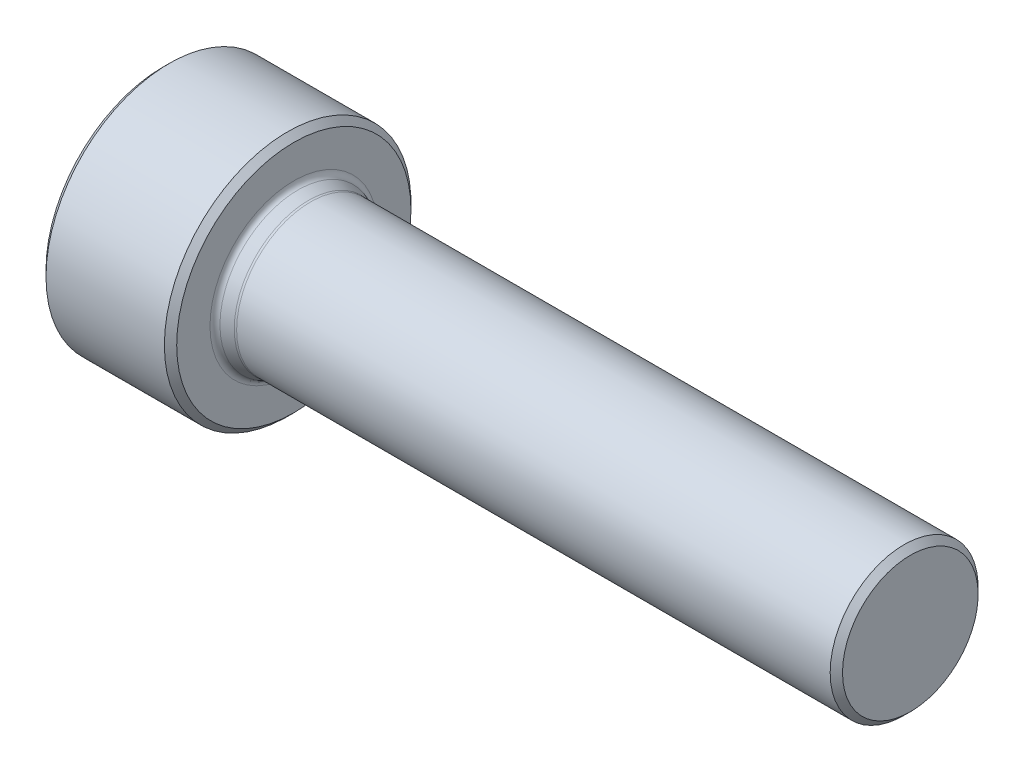
SolidWorks part; units mm, degrees
material "AISI 1020"
ref_plane "Спереди" through (0, 0, 0) normal (0, 0, 1) x (1, 0, 0)
ref_plane "Сверху" through (0, 0, 0) normal (0, 1, 0) x (1, 0, 0)
ref_plane "Справа" through (0, 0, 0) normal (1, 0, 0) x (0, 0, -1)
sketch "Эскиз1" plane through (0, 0, 0) normal (0, 0, 1) x (1, 0, 0)
  line L0 (-1000, 0) -> (49000, 0) construction
  line L1 (-4.9825, 2.5) -> (-5.3, 3.05)
  line L2 (-5.3, 3.05) -> (-5.3, 5)
  line L3 (-5.3, 5) -> (0, 5)
  line L4 (0, 5) -> (0, 3.4)
  line L5 (0.1677, 3.1639) -> (0.5977, 3.0139)
  line L6 (0.68, 3) -> (25, 3)
  line L7 (25, 3) -> (25, 0)
  line L8 (-4.9825, 2.5) -> (-2.3, 2.5)
  line L9 (-2.3, 2.5) -> (-0.8566, 0)
  line L10 (25, 0) -> (-0.8566, 0)
  arc A0 (0.5977, 3.0139) -> (0.68, 3) centre (0.68, 3.25) ccw
  arc A1 (0, 3.4) -> (0.1677, 3.1639) centre (0.25, 3.4) ccw
  dimension "c" = 0.25
  dimension "UGOL" = 60
  dimension "D" = 10
  dimension "t" = 3
  dimension "w" = 2.3
  dimension "l" = 25
  dimension "D_1" = 6.1
  dimension "S" = 5
  dimension "da" = 6.8
  dimension "f" = 0.68
  dimension "_d" = 6
revolve "Повернуть1" add sketch "Эскиз1" angle 360 about L0
sketch "Эскиз2" plane through (-5.3, 0, 0) normal (-1, 0, 0) x (0, 0, 1)
  line L1 (-0.0381, 2.8647) -> (-2.4619, 1.4654)
  line L2 (-2.5, 1.3994) -> (-2.5, -1.3994)
  line L3 (-2.4619, -1.4654) -> (-0.0381, -2.8647)
  line L4 (0.0381, -2.8647) -> (2.4619, -1.4654)
  line L5 (2.5, -1.3994) -> (2.5, 1.3994)
  line L6 (2.4619, 1.4654) -> (0.0381, 2.8647)
  arc A1 (2.4619, -1.4654) -> (2.5, -1.3994) centre (0, 0) ccw
  arc A2 (2.5, 1.3994) -> (2.4619, 1.4654) centre (0, 0) ccw
  arc A3 (0.0381, 2.8647) -> (-0.0381, 2.8647) centre (0, 0) ccw
  arc A4 (-2.4619, 1.4654) -> (-2.5, 1.3994) centre (0, 0) ccw
  arc A5 (-2.5, -1.3994) -> (-2.4619, -1.4654) centre (0, 0) ccw
  arc A6 (-0.0381, -2.8647) -> (0.0381, -2.8647) centre (0, 0) ccw
  dimension "e" = 5.73
  dimension "S" = 5
  dimension "UG1" = 120
  dimension "UG2" = 120
extrude "Вырез-Вытянуть1" cut sketch "Эскиз2" against normal blind 3
chamfer "Фаска1" distance 0.25 angle 45 3 edges at (0, 0, 5) (-5.3, 0, 5) (25, 0, 3)
equation "\"t@Вырез-Вытянуть1\"=1.3"
